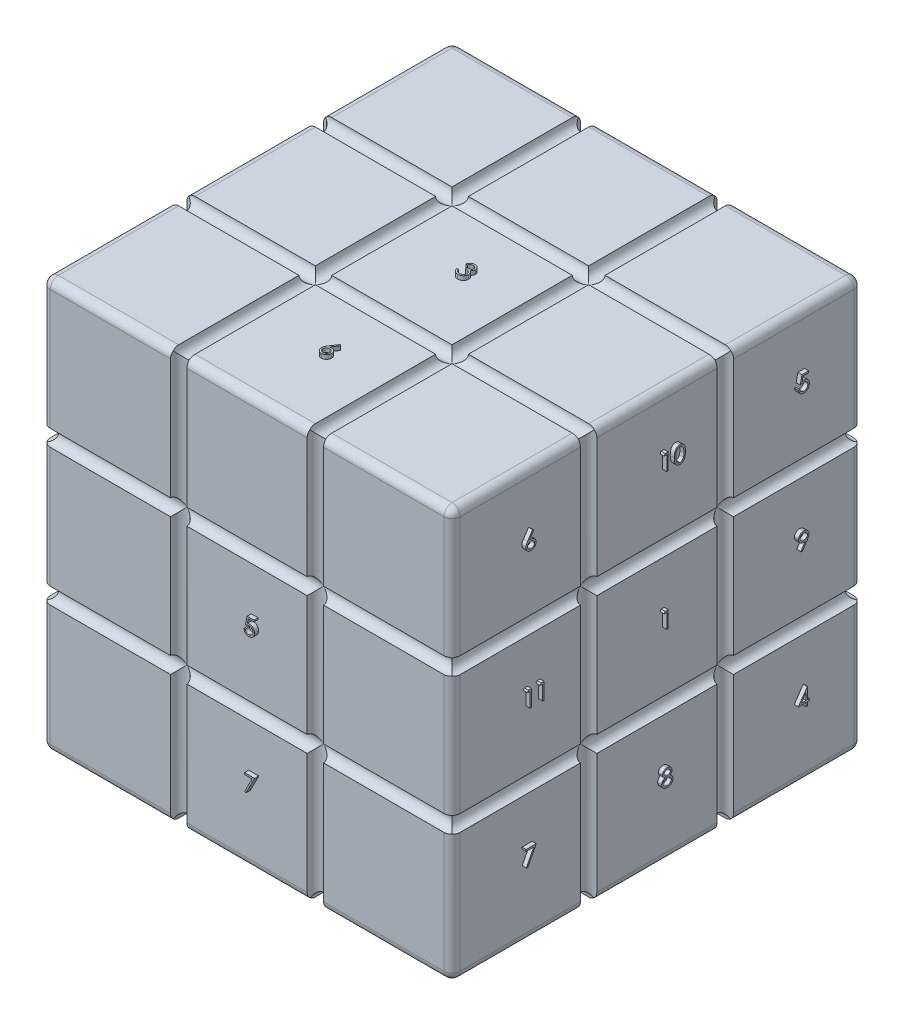
SolidWorks part; units mm, degrees
material "聚脂树脂"
ref_plane "前视基准面" through (0, 0, 0) normal (0, 0, 1) x (1, 0, 0)
ref_plane "上视基准面" through (0, 0, 0) normal (0, 1, 0) x (1, 0, 0)
ref_plane "右视基准面" through (0, 0, 0) normal (1, 0, 0) x (0, 0, -1)
sketch "草图1" plane through (0, 0, 0) normal (0, 1, 0) x (1, 0, 0)
  line L1 (-55.8524, 235.1951) -> (244.1476, 235.1951)
  line L2 (-55.8524, 235.1951) -> (-55.8524, -64.8049)
  line L3 (-55.8524, -64.8049) -> (244.1476, -64.8049)
  line L4 (244.1476, 235.1951) -> (244.1476, -64.8049)
extrude "凸台-拉伸1" add sketch "草图1" along normal blind 300 contours L4 L3 L2 L1
sketch "草图2" plane through (-55.8524, 0, 0) normal (-1, 0, 0) x (0, 0, 1)
  line L0 (-235.1951, 300) -> (64.8049, 300) construction
  line L1 (-235.1951, 300) -> (-235.1951, 0) construction
  line L2 (-235.1951, 0) -> (64.8049, 0) construction
  line L3 (64.8049, 300) -> (64.8049, 0) construction
  circle A0 centre (-135.1951, 300) radius 6
  circle A1 centre (-35.1951, 300) radius 6
  circle A2 centre (-235.1951, 200) radius 6
  circle A3 centre (-235.1951, 100) radius 6
  circle A4 centre (-135.1951, 0) radius 6
  circle A5 centre (-35.1951, 0) radius 6
  circle A6 centre (64.8049, 100) radius 6
  circle A7 centre (64.8049, 200) radius 6
  dimension "D1" = 100
  dimension "D2" = 100
  dimension "D3" = 100
  dimension "D4" = 100
extrude "切除-拉伸1" cut sketch "草图2" against normal through all
sketch "草图3" plane through (0, 0, 0) normal (0, -1, 0) x (1, 0, 0)
  line L0 (-55.8524, -29.1951) -> (-55.8524, -41.1951) construction
  line L1 (-55.8524, -129.1951) -> (-55.8524, -141.1951) construction
  line L2 (244.1476, -41.1951) -> (244.1476, -29.1951) construction
  line L3 (244.1476, -141.1951) -> (244.1476, -129.1951) construction
  line L4 (-55.8524, 64.8049) -> (244.1476, 64.8049) construction
  line L5 (-55.8524, -235.1951) -> (244.1476, -235.1951) construction
  circle A0 centre (-55.8524, -35.1951) radius 6
  circle A1 centre (-55.8524, -135.1951) radius 6
  circle A2 centre (244.1476, -35.1951) radius 6
  circle A3 centre (244.1476, -135.1951) radius 6
  circle A4 centre (44.1476, 64.8049) radius 6
  circle A5 centre (144.1476, 64.8049) radius 6
  circle A6 centre (44.1476, -235.1951) radius 6
  circle A7 centre (144.1476, -235.1951) radius 6
  dimension "D1" = 100
  dimension "D2" = 100
extrude "切除-拉伸2" cut sketch "草图3" against normal through all
sketch "草图5" plane through (0, 0, -235.1951) normal (0, 0, -1) x (-1, 0, 0)
  line L0 (-138.1476, 300) -> (-150.1476, 300) construction
  line L1 (-38.1476, 300) -> (-50.1476, 300) construction
  line L2 (55.8524, 194) -> (55.8524, 206) construction
  line L3 (55.8524, 94) -> (55.8524, 106) construction
  line L4 (-50.1476, 0) -> (-38.1476, 0) construction
  line L5 (-150.1476, 0) -> (-138.1476, 0) construction
  line L6 (-244.1476, 106) -> (-244.1476, 94) construction
  line L7 (-244.1476, 206) -> (-244.1476, 194) construction
  circle A0 centre (-144.1476, 300) radius 6
  circle A1 centre (-44.1476, 300) radius 6
  circle A2 centre (55.8524, 200) radius 6
  circle A3 centre (55.8524, 100) radius 6
  circle A4 centre (-44.1476, 0) radius 6
  circle A5 centre (-144.1476, 0) radius 6
  circle A6 centre (-244.1476, 100) radius 6
  circle A7 centre (-244.1476, 200) radius 6
extrude "切除-拉伸3" cut sketch "草图5" against normal through all
fillet "圆角1" radius 6 36 edges at (197.1476, 0, 64.8049) (94.1476, 0, 64.8049) (-8.8524, 0, 64.8049) (-55.8524, 253, 64.8049) (-55.8524, 150, 64.8049) (-55.8524, 47, 64.8049) (-55.8524, 0, 17.8049) (-55.8524, 0, -85.1951) (-55.8524, 0, -188.1951) (-55.8524, 253, -235.1951) (-55.8524, 150, -235.1951) (-55.8524, 47, -235.1951) (-8.8524, 0, -235.1951) (94.1476, 0, -235.1951) (197.1476, 0, -235.1951) (244.1476, 0, -188.1951) (244.1476, 0, -85.1951) (244.1476, 0, 17.8049) (244.1476, 47, 64.8049) (244.1476, 150, 64.8049) (244.1476, 253, 64.8049) (244.1476, 47, -235.1951) (244.1476, 150, -235.1951) (244.1476, 253, -235.1951) (197.1476, 300, 64.8049) (94.1476, 300, 64.8049) (-8.8524, 300, 64.8049) (-55.8524, 300, 17.8049) (-55.8524, 300, -85.1951) (-55.8524, 300, -188.1951) (-8.8524, 300, -235.1951) (94.1476, 300, -235.1951) (197.1476, 300, -235.1951) (244.1476, 300, -188.1951) (244.1476, 300, -85.1951) (244.1476, 300, 17.8049)
sketch "草图8" plane through (-55.8524, 0, 0) normal (-1, 0, 0) x (0, 0, 1)
  text T0 "0" font "Century Gothic" height 12
  text T1 "0" font "Century Gothic" height 12
  text T2 "1" font "Century Gothic" height 12
  text T3 "2" font "Century Gothic" height 12
  text T4 "3" font "Century Gothic" height 12
  text T5 "0" font "Century Gothic" height 12
  text T6 "1" font "Century Gothic" height 12
  text T7 "2" font "Century Gothic" height 12
  text T8 "3" font "Century Gothic" height 12
sketch "草图9" plane through (244.1476, 0, 0) normal (1, 0, 0) x (0, 0, -1)
  text T0 "1" font "Century Gothic" height 12
  text T1 "4" font "Century Gothic" height 12
  text T2 "5" font "Century Gothic" height 12
  text T3 "6" font "Century Gothic" height 12
  text T4 "7" font "Century Gothic" height 12
  text T5 "8" font "Century Gothic" height 12
  text T6 "9" font "Century Gothic" height 12
  text T7 "10" font "Century Gothic" height 12
  text T8 "11" font "Century Gothic" height 12
sketch "草图10" plane through (0, 0, 0) normal (0, -1, 0) x (-1, 0, 0)
  text T0 "2" font "Century Gothic" height 12
  text T1 "4" font "Century Gothic" height 12
sketch "草图11" plane through (0, 0, -235.1951) normal (0, 0, -1) x (-1, 0, 0)
  text T0 "4" font "Century Gothic" height 12
  text T1 "5" font "Century Gothic" height 12
sketch "草图12" plane through (0, 300, 0) normal (0, 1, 0) x (1, 0, 0)
  text T0 "3" font "Century Gothic" height 12
  text T1 "6" font "Century Gothic" height 12
sketch "草图13" plane through (0, 0, 64.8049) normal (0, 0, 1) x (1, 0, 0)
  text T0 "5" font "Century Gothic" height 12
  text T1 "7" font "Century Gothic" height 12
extrude "凸台-拉伸2" add sketch "草图8" along normal blind 3
extrude "凸台-拉伸3" add sketch "草图9" along normal blind 3
extrude "凸台-拉伸4" add sketch "草图10" along normal blind 3
extrude "凸台-拉伸5" add sketch "草图11" along normal blind 3
extrude "凸台-拉伸6" add sketch "草图12" along normal blind 3
extrude "凸台-拉伸7" add sketch "草图13" along normal blind 3
